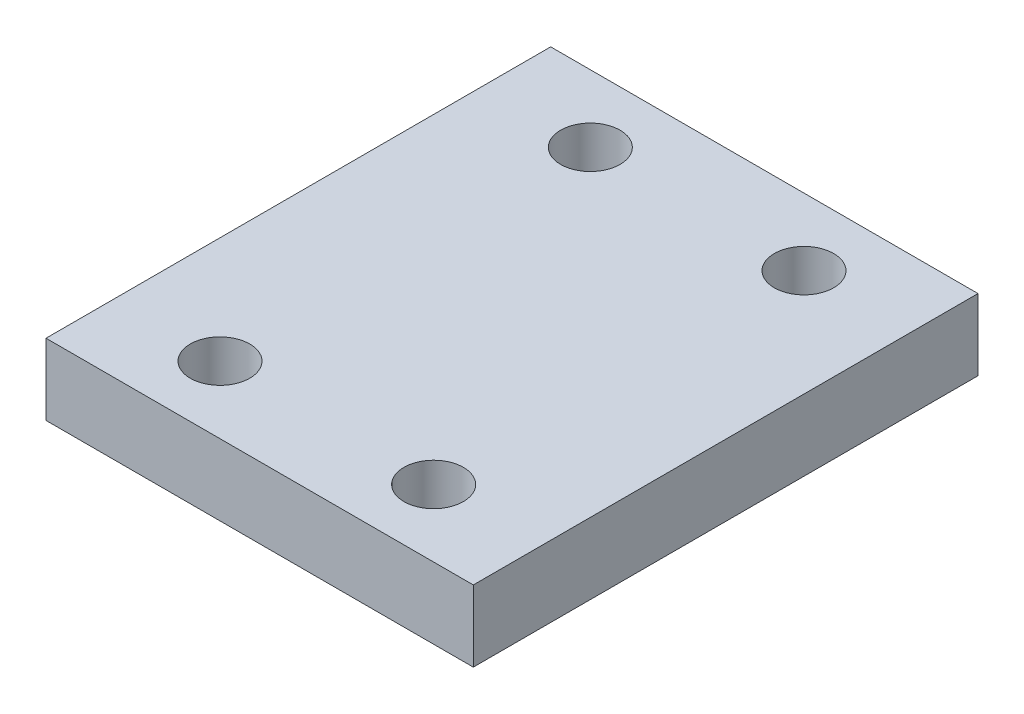
SolidWorks part; units mm, degrees
ref_plane "Front" through (0, 0, 0) normal (0, 0, 1) x (1, 0, 0)
ref_plane "Top" through (0, 0, 0) normal (0, 1, 0) x (1, 0, 0)
ref_plane "Right" through (0, 0, 0) normal (1, 0, 0) x (0, 0, -1)
sketch "Sketch1" plane through (0, 0, 0) normal (0, 1, 0) x (1, 0, 0)
  line L1 (-9.525, 16.51) -> (9.525, 16.51) construction
  line L2 (-9.525, 16.51) -> (-9.525, -16.51) construction
  line L3 (-9.525, -16.51) -> (9.525, -16.51) construction
  line L4 (9.525, 16.51) -> (9.525, -16.51) construction
  line L5 (-9.525, 16.51) -> (9.525, -16.51) construction
  line L6 (-9.525, -16.51) -> (9.525, 16.51) construction
  line L7 (-19.05, -22.5) -> (19.05, -22.5)
  line L8 (-19.05, -22.5) -> (-19.05, 22.5)
  line L9 (-19.05, 22.5) -> (19.05, 22.5)
  line L10 (19.05, -22.5) -> (19.05, 22.5)
  line L11 (-19.05, -22.5) -> (19.05, 22.5) construction
  line L12 (-19.05, 22.5) -> (19.05, -22.5) construction
  circle A0 centre (-9.525, 16.51) radius 2.65
  circle A1 centre (9.525, 16.51) radius 2.65
  circle A2 centre (9.525, -16.51) radius 2.65
  circle A3 centre (-9.525, -16.51) radius 2.65
  point P0 (0, 0)
  point P5 (0, 0)
  dimension "D5" = 5.3
  dimension "D1" = 33.02
  dimension "D2" = 19.05
  dimension "D3" = 38.1
  dimension "D4" = 45
extrude "Boss-Extrude1" add sketch "Sketch1" along normal blind 6.35
